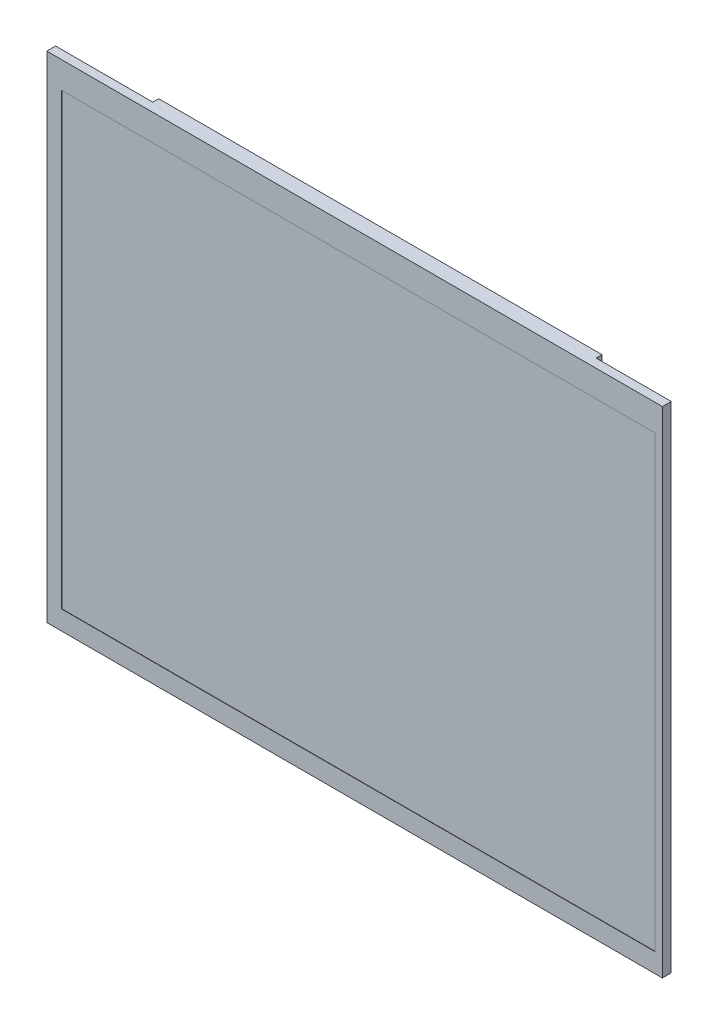
SolidWorks part; units mm, degrees
ref_plane "前视基准面" through (0, 0, 0) normal (0, 0, 1) x (1, 0, 0)
ref_plane "上视基准面" through (0, 0, 0) normal (0, 1, 0) x (1, 0, 0)
ref_plane "右视基准面" through (0, 0, 0) normal (1, 0, 0) x (0, 0, -1)
other "Configuration Table"
sketch "草图1" plane through (0, 0, 0) normal (0, 0, 1) x (1, 0, 0)
  line L1 (0, 0) -> (209, 0)
  line L2 (0, 0) -> (0, 168)
  line L3 (0, 168) -> (209, 168)
  line L4 (209, 0) -> (209, 168)
  line L5 (0, 168) -> (209, 168) construction
  line L6 (0, 168) -> (0, 159) construction
  line L7 (0, 159) -> (209, 159) construction
  line L8 (209, 168) -> (209, 159) construction
  line L9 (0, 0) -> (209, 0) construction
  line L10 (0, 0) -> (0, 6.5) construction
  line L11 (0, 6.5) -> (209, 6.5) construction
  line L12 (209, 0) -> (209, 6.5) construction
  line L13 (0, 168) -> (5, 168) construction
  line L14 (0, 168) -> (0, 0) construction
  line L15 (0, 0) -> (5, 0) construction
  line L16 (5, 168) -> (5, 0) construction
  line L17 (209, 168) -> (206.5, 168) construction
  line L18 (209, 168) -> (209, 0) construction
  line L19 (209, 0) -> (206.5, 0) construction
  line L20 (206.5, 168) -> (206.5, 0) construction
  line L21 (5, 159) -> (206.5, 159)
  line L22 (5, 159) -> (5, 6.5)
  line L23 (5, 6.5) -> (206.5, 6.5)
  line L24 (206.5, 159) -> (206.5, 6.5)
extrude "1-1" add sketch "草图1" along normal blind 3
extrude "1-2" add sketch "草图1<3>" along normal blind 2.9 contours L24 L21 L22 L23 region at (105.75, 82.75, 0)
sketch "草图1<3>" plane through (0, 0, 0) normal (0, 0, 1) x (1, 0, 0) same geometry as "草图1"
sketch "草图3" plane through (0, 0, 0) normal (0, 0, -1) x (-1, 0, 0)
  line L1 (-209, 168) -> (-183.5, 168) construction
  line L2 (-209, 168) -> (-209, 159) construction
  line L3 (-209, 159) -> (-183.5, 159) construction
  line L4 (-183.5, 168) -> (-183.5, 159) construction
  line L5 (0, 168) -> (-33, 168) construction
  line L6 (0, 168) -> (0, 159) construction
  line L7 (0, 159) -> (-33, 159) construction
  line L8 (-33, 168) -> (-33, 159) construction
  line L9 (-183.5, 168) -> (-33, 168)
  line L10 (-183.5, 168) -> (-183.5, 159)
  line L11 (-183.5, 159) -> (-33, 159)
  line L12 (-33, 168) -> (-33, 159)
extrude "2-1" add sketch "草图3" along normal blind 2
